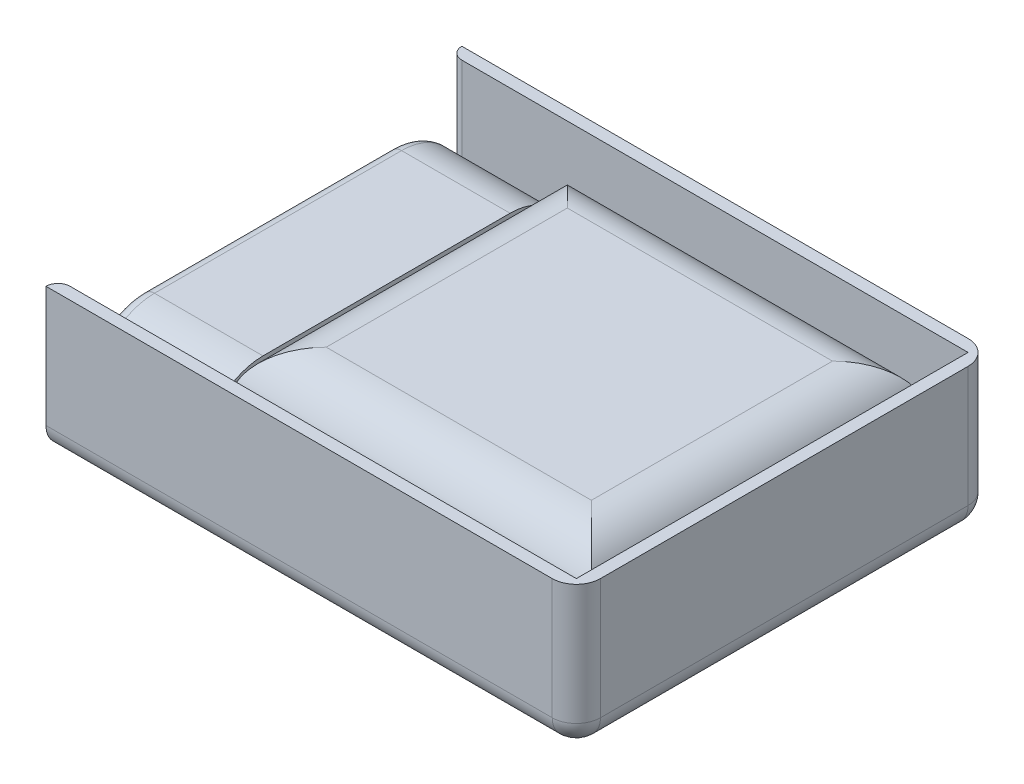
SolidWorks part; units mm, degrees
ref_plane "Front Plane" through (0, 0, 0) normal (0, 0, 1) x (1, 0, 0)
ref_plane "Top Plane" through (0, 0, 0) normal (0, 1, 0) x (1, 0, 0)
ref_plane "Right Plane" through (0, 0, 0) normal (1, 0, 0) x (0, 0, -1)
sketch "Sketch1" plane through (0, 0, 0) normal (0, 1, 0) x (1, 0, 0)
  line L1 (-11, 8.625) -> (11, 8.625)
  line L2 (-11, 8.625) -> (-11, -8.625)
  line L3 (-11, -8.625) -> (11, -8.625)
  line L4 (11, 8.625) -> (11, -8.625)
  line L5 (-11, 8.625) -> (11, -8.625) construction
  line L6 (-11, -8.625) -> (11, 8.625) construction
  point P0 (0, 0)
  dimension "D1" = 22
  dimension "D2" = 17.25
extrude "Boss-Extrude1" add sketch "Sketch1" along normal blind 6
sketch "Sketch2" plane through (0, 6, 0) normal (0, 1, 0) x (1, 0, 0)
  line L0 (-11, 8.625) -> (-11, -8.625) construction
  line L1 (-5, 7) -> (10, 7)
  line L2 (-5, 7) -> (-5, -7)
  line L3 (-5, -7) -> (10, -7)
  line L4 (10, 7) -> (10, -7)
  line L5 (11, -8.625) -> (11, 8.625) construction
  line L6 (0, 0) -> (-12.8914, 0) construction
  line L7 (11, 8.625) -> (-11, 8.625) construction
  line L8 (-11, -8.125) -> (10.5, -8.125)
  line L9 (-11, -8.125) -> (-11, 8.125)
  line L10 (-11, 8.125) -> (10.5, 8.125)
  line L11 (10.5, -8.125) -> (10.5, 8.125)
  line L12 (-11, -8.625) -> (11, -8.625) construction
  dimension "D1" = 14
  dimension "D2" = 6
  dimension "D3" = 1
  dimension "D4" = 7
  dimension "D5" = 0.5
  dimension "D6" = 0.5
  dimension "D7" = 0.5
extrude "Cut-Extrude1" cut sketch "Sketch2" against normal blind 5.5
fillet "Fillet1" radius 2 4 edges at (10, 6, 0) (2.5, 6, 7) (-5, 6, 0) (2.5, 6, -7)
fillet "Fillet2" radius 0.5 10 edges at (-11, 3.25, -8.125) (-11, 3.25, 8.125) (-0.25, 0.5, -8.125) (10.5, 0.5, 0) (-0.25, 0.5, 8.125) (-11, 0.5, 0) (2.5, 0.5, 7) (10, 0.5, 0) (2.5, 0.5, -7) (-5, 0.5, 0)
sketch "Sketch3" plane through (0, 0.5, 0) normal (0, 1, 0) x (1, 0, 0)
  line L1 (-5.5, -7.625) -> (-10.5, -7.625)
  line L2 (-5.5, -7.625) -> (-5.5, 7.625)
  line L3 (-5.5, 7.625) -> (-10.5, 7.625)
  line L4 (-10.5, -7.625) -> (-10.5, 7.625)
  line L5 (-5.5, -7.625) -> (-10.5, 7.625) construction
  line L6 (-5.5, 7.625) -> (-10.5, -7.625) construction
  point P0 (-8, 0)
  dimension "D1" = 5
extrude "Boss-Extrude2" add sketch "Sketch3" along normal blind 4
fillet "Fillet3" radius 2.5 2 edges at (-8, 4.5, 7.625) (-8, 4.5, -7.625)
fillet "Fillet6" radius 0.5 5 edges at (-10.5, 1.25, -7.625) (-10.5, 3.7678, -6.8928) (-10.5, 1.25, 7.625) (-10.5, 3.7678, 6.8928) (-10.5, 4.5, 0)
fillet "Fillet7" radius 1 5 edges at (0, 0, -8.625) (11, 3, -8.625) (11, 0, 0) (11, 3, 8.625) (0, 0, 8.625)
